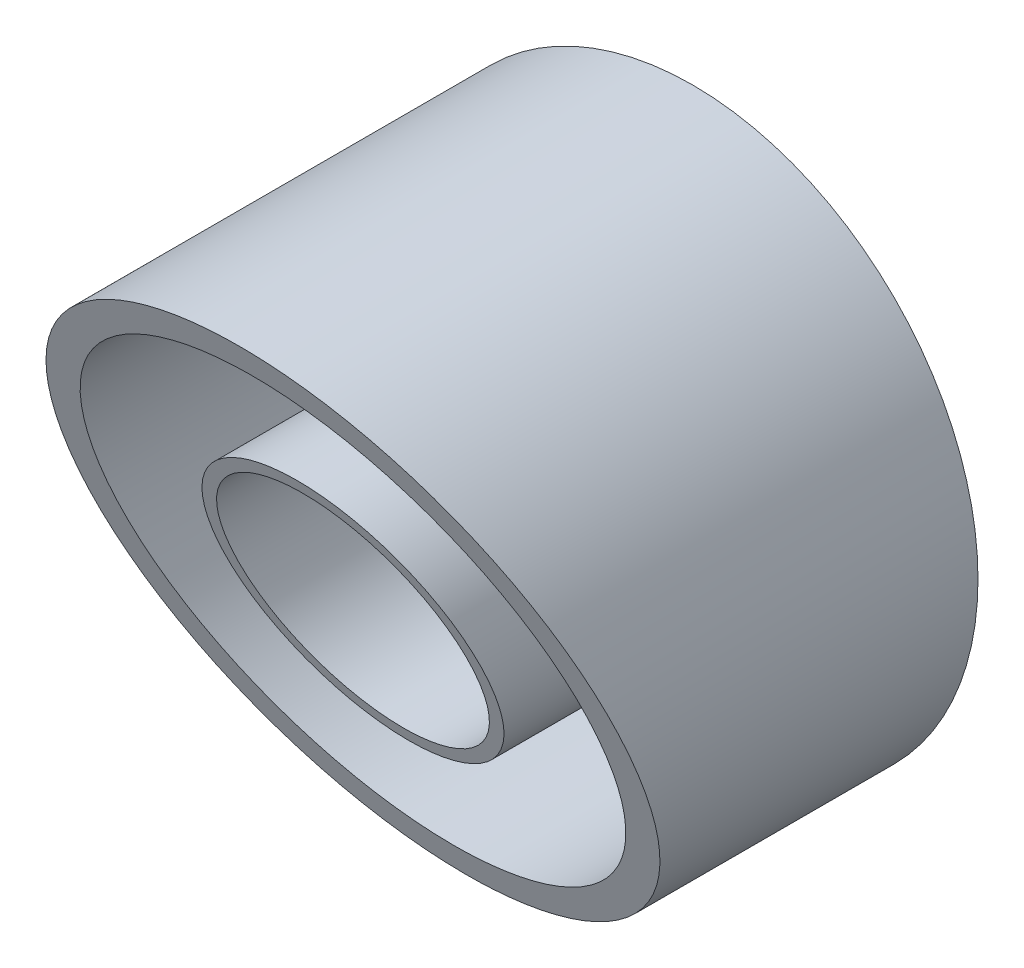
SolidWorks part; units mm, degrees
ref_plane "Front Plane" through (0, 0, 0) normal (0, 0, 1) x (1, 0, 0)
ref_plane "Top Plane" through (0, 0, 0) normal (0, 1, 0) x (1, 0, 0)
ref_plane "Right Plane" through (0, 0, 0) normal (1, 0, 0) x (0, 0, -1)
sketch "Sketch1" plane through (0, 0, 0) normal (0, 0, 1) x (1, 0, 0)
  circle A0 centre (0, 0) radius 14
  circle A1 centre (0, 0) radius 15.5
extrude "Boss-Extrude2" add sketch "Sketch1" along normal blind 50
sketch "Sketch3" plane through (0, 0, 0) normal (0, 0, 1) x (1, 0, 0)
  circle A0 centre (0, 0) radius 28
  circle A1 centre (0, 0) radius 31.5
extrude "Boss-Extrude3" add sketch "Sketch3" along normal blind 50 separate body
sketch "Sketch4" plane through (0, 0, 0) normal (1, 0, 0) x (0, 0, -1)
  line L0 (-50, 31.5) -> (-25, -31.5)
  line L1 (-50, -31.5) -> (0, -31.5) construction
  line L2 (-25, -31.5) -> (-50, -31.5)
  line L3 (-50, 31.5) -> (-50, -31.5) construction
  line L4 (-50, 31.5) -> (-50, -31.5)
extrude "Cut-Extrude1" cut sketch "Sketch4" against normal blind 10216 and the other way blind 2500 contours L4 L2 L0
sketch "Sketch15" plane through (0, 0, 0) normal (0, 0, -1) x (-1, 0, 0)
  circle A0 centre (0, 0) radius 15.5
  circle A1 centre (0, 0) radius 27.9625
extrude "Boss-Extrude4" add sketch "Sketch15" against normal blind 3
